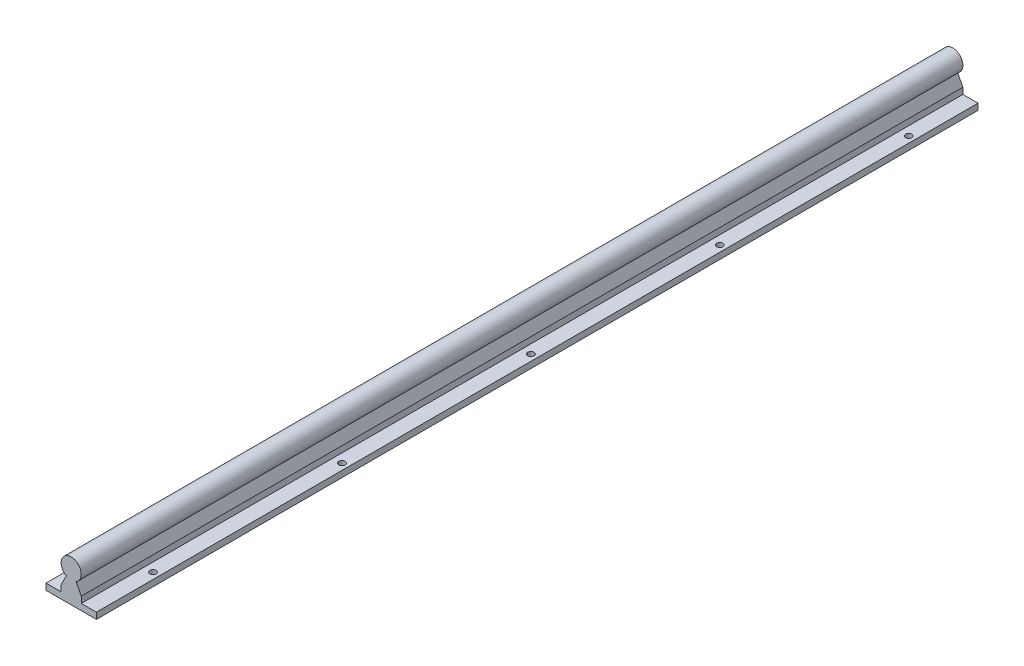
SolidWorks part; units mm, degrees
ref_plane "Front Plane" through (0, 0, 0) normal (0, 0, 1) x (1, 0, 0)
ref_plane "Top Plane" through (0, 0, 0) normal (0, 1, 0) x (1, 0, 0)
ref_plane "Right Plane" through (0, 0, 0) normal (1, 0, 0) x (0, 0, -1)
sketch "Sketch2" plane through (0, 0, 0) normal (0, 0, 1) x (1, 0, 0)
  line L0 (-20, 0) -> (20, 0)
  line L1 (20, 0) -> (20, 5)
  line L2 (-20, 0) -> (-20, 5)
  line L3 (-20, 5) -> (-8, 5)
  line L4 (20, 5) -> (8, 5)
  line L5 (-8, 5) -> (-8, 10)
  line L6 (8, 5) -> (8, 10)
  line L8 (-8, 10) -> (-3.873, 18)
  line L9 (8, 10) -> (3.873, 18)
  circle A0 centre (0, 25) radius 8
  dimension "D1" = 16
  dimension "D2" = 40
  dimension "D3" = 5
  dimension "D4" = 5
  dimension "D5" = 25
  dimension "D6" = 12
  dimension "D7" = 12
  dimension "D8" = 5
  dimension "D9" = 5
  dimension "D10" = 20
extrude "Boss-Extrude3" add sketch "Sketch2" along normal blind 700 contours A0 L8 L5 L3 L2 L0 L1 L4 L6 L9 region at (0, 6.2033, 0)
extrude "Boss-Extrude4" add sketch "Sketch2<4>" along normal blind 700 contours A0 region at (0, 25, 0)
sketch "Sketch2<4>" plane through (0, 0, 0) normal (0, 0, 1) x (1, 0, 0) same geometry as "Sketch2"
hole_wizard "Ø5.0mm Dowel Hole1" positions "Sketch4" profile "Sketch3" hole size "Ø5.0" standard "ISO" end condition through all
sketch "Sketch4" plane through (0, 5, 0) normal (0, 1, 0) x (1, 0, 0)
  line L0 (20, -700) -> (20, 0) construction
  line L1 (-20, -700) -> (-20, 0) construction
  line L2 (20, -700) -> (8, -700) construction
  line L3 (-20, -700) -> (-8, -700) construction
  point P0 (15, -650)
  point P2 (-15, -650)
  point P11 (-14, -700)
  dimension "D1" = 5
  dimension "D2" = 5
  dimension "D3" = 50
  dimension "D4" = 50
sketch "Sketch3" plane through (15, 5, 650) normal (1, 0, 0) x (0, 0, 1)
  line L0 (0, 0) -> (0, 5)
  line L1 (0, 5) -> (2.5, 5)
  line L2 (2.5, 5) -> (2.5, 0)
  line L5 (2.5, 0) -> (0, 0)
  line L11 (0, -6.35) -> (0, 107.95) construction
  dimension "Thru Hole Dia." = 5
  dimension "Thru Hole Depth" = 5
pattern_linear "LPattern1" count 5 spacing 150 along (0, 0, -1) of "Ø5.0mm Dowel Hole1"
